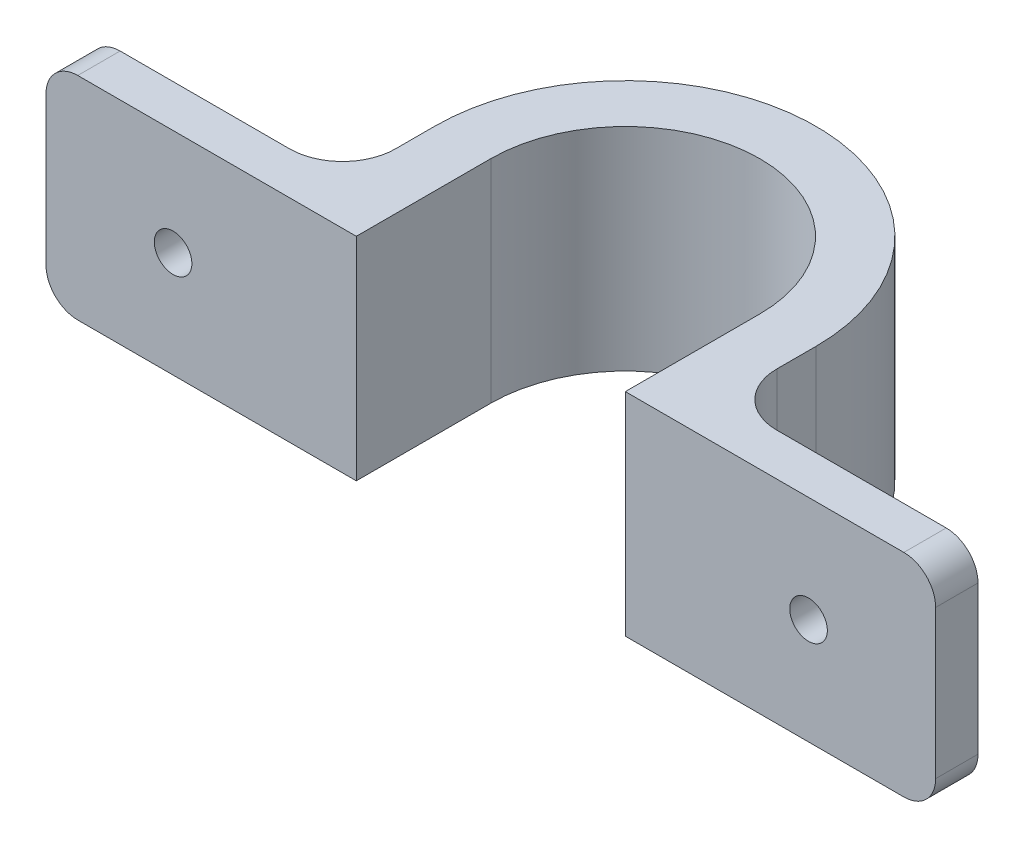
SolidWorks part; units mm, degrees
ref_plane "Front Plane" through (0, 0, 0) normal (0, 0, 1) x (1, 0, 0)
ref_plane "Top Plane" through (0, 0, 0) normal (0, 1, 0) x (1, 0, 0)
ref_plane "Right Plane" through (0, 0, 0) normal (1, 0, 0) x (0, 0, -1)
sketch "Sketch1" plane through (0, 0, 0) normal (0, 1, 0) x (1, 0, 0)
  line L0 (0, 0) -> (0, 4)
  line L1 (0, 4) -> (24, 4)
  line L2 (60, 4) -> (84, 4)
  line L3 (84, 4) -> (84, 0)
  line L6 (29.3, 12.7) -> (29.3, 0)
  line L7 (29.3, 0) -> (0, 0)
  line L8 (54.7, 12.7) -> (54.7, 0)
  line L9 (54.7, 0) -> (84, 0)
  line L10 (29.3, 12.7) -> (54.7, 12.7) construction
  line L11 (24, 12.7) -> (24, 4)
  line L12 (60, 12.7) -> (60, 4)
  line L13 (12, 4) -> (12, 0) construction
  line L14 (72, 4) -> (72, 0) construction
  arc A1 (54.7, 12.7) -> (29.3, 12.7) centre (42, 12.7) ccw
  arc A2 (60, 12.7) -> (24, 12.7) centre (42, 12.7) ccw
  point P18 (0, 0)
  dimension "D3" = 12.7
  dimension "D4" = 18
  dimension "D1" = 12.7
  dimension "D2" = 4
  dimension "D5" = 60
extrude "Boss-Extrude1" add sketch "Sketch1" along normal blind 20
sketch "Sketch2" plane through (0, 0, -4) normal (0, 0, -1) x (-1, 0, 0)
  line L0 (-42, 20) -> (-42, 0) construction
  line L1 (-24, 20) -> (-60, 20) construction
  line L2 (-60, 0) -> (-24, 0) construction
  line L3 (-72, 10) -> (-42, 10) construction
  line L4 (-42, 10) -> (-12, 10) construction
  circle A1 centre (-72, 10) radius 1.775
  circle A2 centre (-12, 10) radius 1.775
  dimension "D1" = 3.55
  dimension "D2" = 60
extrude "Cut-Extrude1" cut sketch "Sketch2" against normal through all
fillet "Fillet1" radius 3 4 edges at (0, 0, -2) (0, 20, -2) (84, 0, -2) (84, 20, -2)
fillet "Fillet2" radius 5 2 edges at (60, 10, -4) (24, 10, -4)
